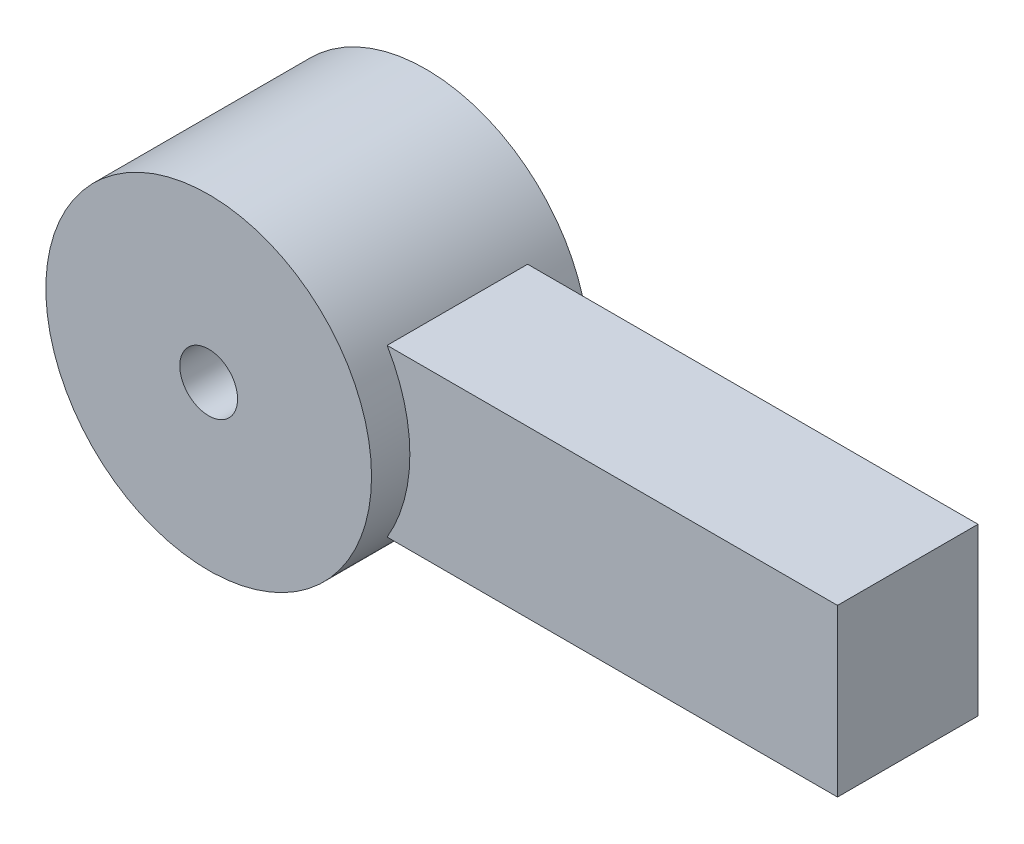
SolidWorks part; units mm, degrees
ref_plane "Front" through (0, 0, 0) normal (0, 0, 1) x (1, 0, 0)
ref_plane "Top" through (0, 0, 0) normal (0, 1, 0) x (1, 0, 0)
ref_plane "Right" through (0, 0, 0) normal (1, 0, 0) x (0, 0, -1)
sketch "Sketch1" plane through (0, 0, 0) normal (0, 0, 1) x (1, 0, 0)
  line L0 (0, 0) -> (57.5688, 0) construction
  line L1 (46.2262, -6.4982) -> (10.9688, -6.4982)
  line L2 (46.2262, -6.4982) -> (46.2262, 6.4982)
  line L3 (46.2262, 6.4982) -> (10.9688, 6.4982)
  line L5 (46.2262, -6.4982) -> (10.9688, 6.4982) construction
  line L6 (46.2262, 6.4982) -> (10.9688, -6.4982) construction
  line L7 (20.9544, -6.4982) -> (20.9544, 6.4982) construction
  circle A0 centre (0, 0) radius 12.7492
  circle A1 centre (0, 0) radius 2.2616
  point P3 (28.5975, 0)
extrude "Boss-Extrude1" add sketch "Sketch1" along normal mid plane 11 contours A0 L1 L2 L3 region at (29.1958, 0, 0)
extrude "Boss-Extrude2" add sketch "Sketch1<3>" along normal mid plane 17 contours A0 A1 region at (-12.3886, 0, 0)
sketch "Sketch1<3>" plane through (0, 0, 0) normal (0, 0, 1) x (1, 0, 0) same geometry as "Sketch1"
